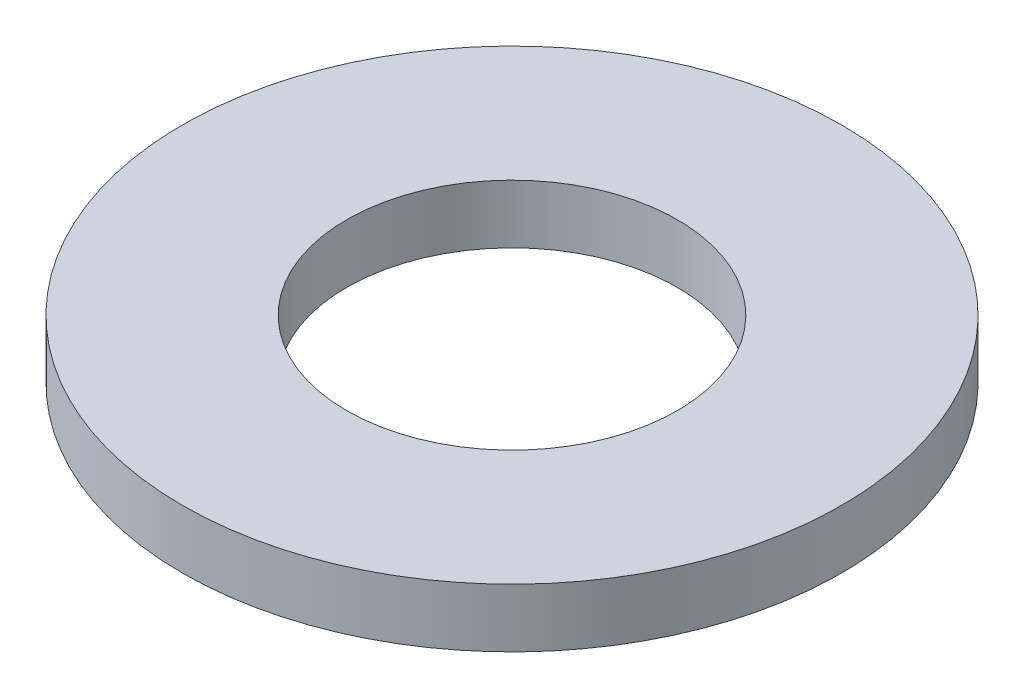
SolidWorks part; units mm, degrees
ref_plane "Front Plane" through (0, 0, 0) normal (0, 0, 1) x (1, 0, 0)
ref_plane "Top Plane" through (0, 0, 0) normal (0, 1, 0) x (1, 0, 0)
ref_plane "Right Plane" through (0, 0, 0) normal (1, 0, 0) x (0, 0, -1)
sketch "Sketch1" plane through (0, 0, 0) normal (0, 1, 0) x (1, 0, 0)
  circle A0 centre (0, 0) radius 3.5687
  dimension "OD" = 7.1374
extrude "Boss-Extrude1" add sketch "Sketch1" along normal blind 0.635
sketch "Sketch5" plane through (0, 0.635, 0) normal (0, 1, 0) x (-1, 0, 0)
  circle A0 centre (0, 0) radius 1.7907
  dimension "ID" = 3.5814
extrude "Cut-Extrude1" cut sketch "Sketch5" against normal through all
ref_axis "Axis1" through (0, 0.6668, 0) along (0, -1, 0)
